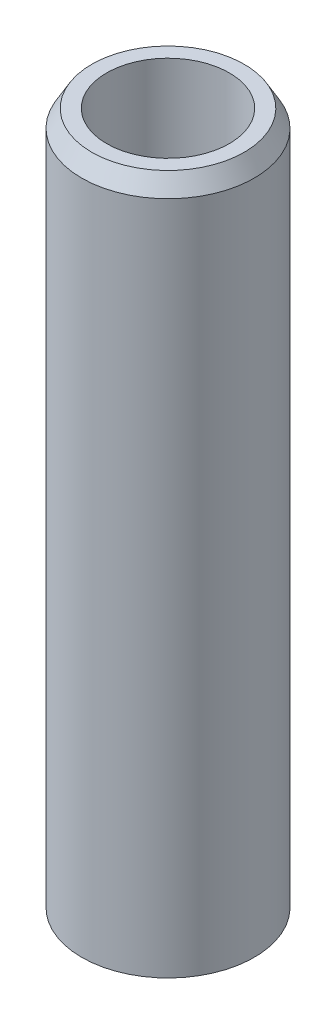
SolidWorks part; units mm, degrees
ref_plane "Front Plane" through (0, 0, 0) normal (0, 0, 1) x (1, 0, 0)
ref_plane "Top Plane" through (0, 0, 0) normal (0, 1, 0) x (1, 0, 0)
ref_plane "Right Plane" through (0, 0, 0) normal (1, 0, 0) x (0, 0, -1)
sketch "Sketch1" plane through (0, 0, 0) normal (0, 1, 0) x (1, 0, 0)
  circle A0 centre (0, 0) radius 17.5
  dimension "SHAFT_OD" = 35
extrude "Boss-Extrude1" add sketch "Sketch1" along normal blind 142.4248
sketch "Sketch2" plane through (0, 0, 0) normal (0, 1, 0) x (1, 0, 0)
  circle A0 centre (0, 0) radius 12.4402
  dimension "BORE_D" = 24.8804
extrude "Cut-Extrude1" cut sketch "Sketch2" along normal through all
chamfer "Chamfer1" distance 3.5235 angle 30 2 edges at (0, 142.4248, 17.5) (0, 0, 17.5) first distance on face at (0, 142.4248, 17.5) first distance on face at (0, 0, 12.4402)
